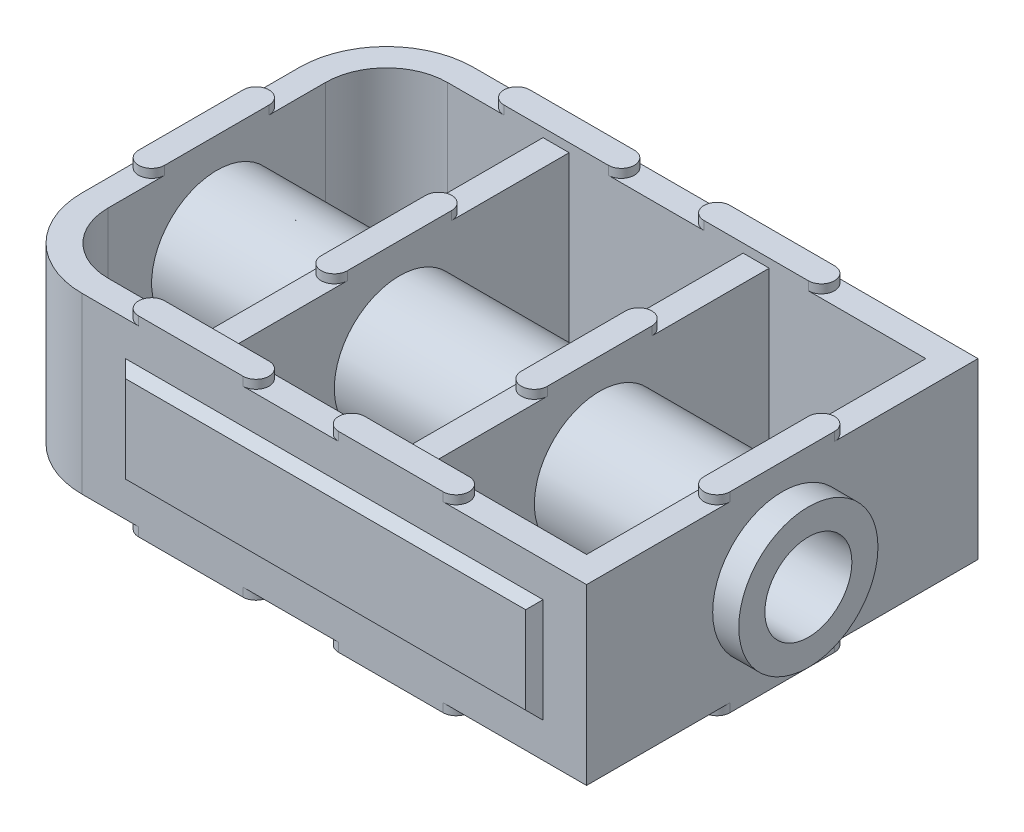
SolidWorks part; units mm, degrees
ref_plane "Front Plane" through (0, 0, 0) normal (0, 0, 1) x (1, 0, 0)
ref_plane "Top Plane" through (0, 0, 0) normal (0, 1, 0) x (1, 0, 0)
ref_plane "Right Plane" through (0, 0, 0) normal (1, 0, 0) x (0, 0, -1)
sketch "Sketch1" plane through (0, 0, 0) normal (0, 1, 0) x (1, 0, 0)
  line L0 (-3, 19.5) -> (-21, 19.5)
  line L1 (0, -22.5) -> (-58, -22.5)
  line L2 (0, -22.5) -> (0, 22.5)
  line L3 (0, 22.5) -> (-58, 22.5)
  line L4 (-68, -12.5) -> (-68, 12.5)
  line L5 (-65, -12.5) -> (-65, 12.5)
  line L6 (-3, -19.5) -> (-21, -19.5)
  line L7 (-3, -19.5) -> (-3, 19.5)
  line L8 (-47, 19.5) -> (-47, -19.5)
  line L9 (-44, -19.5) -> (-44, 19.5)
  line L10 (-24, -19.5) -> (-24, 19.5)
  line L11 (-21, 19.5) -> (-21, -19.5)
  line L12 (-47, 19.5) -> (-58, 19.5)
  line L13 (-47, -19.5) -> (-58, -19.5)
  line L14 (-3, 19.5) -> (-58, 19.5) construction
  line L15 (-24, -19.5) -> (-44, -19.5)
  line L16 (-3, -19.5) -> (-58, -19.5) construction
  line L17 (-24, 19.5) -> (-44, 19.5)
  arc A0 (-58, -22.5) -> (-68, -12.5) centre (-58, -12.5) cw
  arc A1 (-58, 22.5) -> (-68, 12.5) centre (-58, 12.5) ccw
  arc A2 (-58, 19.5) -> (-65, 12.5) centre (-58, 12.5) ccw
  arc A3 (-58, -19.5) -> (-65, -12.5) centre (-58, -12.5) cw
  point P4 (0, 0)
  point P8 (-68, -22.5)
  point P11 (-68, 22.5)
  dimension "D3" = 10
  dimension "D1" = 68
  dimension "D2" = 45
  dimension "D5" = 3
  dimension "D6" = 3
  dimension "D7" = 18
  dimension "D8" = 18
  dimension "D4" = 3
extrude "Boss-Extrude1" add sketch "Sketch1" along normal mid plane 20
sketch "Sketch3" plane through (0, 0, 0) normal (1, 0, 0) x (0, 0, -1)
  line L0 (-22.5, 10) -> (-22.5, -10) construction
  circle A0 centre (0, 0) radius 7.5
  point P7 (-22.5, 0)
  dimension "D1" = 15
extrude "Boss-Extrude3" add sketch "Sketch3" against normal up to surface (65 mm away) up to face at (-65, 0, 0)
sketch "Sketch4" plane through (0, 0, 0) normal (1, 0, 0) x (0, 0, -1)
  line L0 (-22.5, 10) -> (-22.5, -10) construction
  circle A0 centre (0, 0) radius 5
  point P7 (-22.5, 0)
  dimension "D1" = 10
extrude "Cut-Extrude1" cut sketch "Sketch4" against normal up to surface (68 mm away) up to face at (-68, 0, 0)
sketch "Sketch5" plane through (-68, 0, 0) normal (-1, 0, 0) x (0, 0, 1)
  line L1 (3.4641, 6) -> (-3.4641, 6)
  line L2 (-3.4641, 6) -> (-6.9282, 0)
  line L3 (-6.9282, 0) -> (-3.4641, -6)
  line L4 (-3.4641, -6) -> (3.4641, -6)
  line L5 (3.4641, -6) -> (6.9282, 0)
  line L6 (6.9282, 0) -> (3.4641, 6)
  circle A0 centre (0, 0) radius 6 construction
  dimension "D1" = 12
extrude "Cut-Extrude2" cut sketch "Sketch5" against normal blind 5
sketch "Sketch6" plane through (0, 0, 0) normal (1, 0, 0) x (0, 0, -1)
  circle A0 centre (0, 0) radius 5 construction
  circle A1 centre (0, 0) radius 5
  circle A2 centre (0, 0) radius 8
  dimension "D1" = 16
extrude "Boss-Extrude4" add sketch "Sketch6" along normal blind 3
sketch "Sketch7" plane through (0, 10, 0) normal (0, 1, 0) x (1, 0, 0)
  line L0 (-16.5, 21) -> (-28.5, 21) construction
  line L1 (-16.5, 19.5) -> (-28.5, 19.5)
  line L2 (-16.5, 22.5) -> (-28.5, 22.5)
  line L3 (-51.5, 21) -> (-39.5, 21) construction
  line L4 (-51.5, 22.5) -> (-39.5, 22.5)
  line L5 (-51.5, 19.5) -> (-39.5, 19.5)
  line L6 (0, 0) -> (-78.1897, 0) construction
  line L7 (-24, 19.5) -> (-44, 19.5) construction
  line L8 (0, 22.5) -> (-58, 22.5) construction
  line L9 (-44, 19.5) -> (-44, -19.5) construction
  line L10 (-16.5, -21) -> (-28.5, -21) construction
  line L11 (-16.5, -19.5) -> (-28.5, -19.5)
  line L12 (-16.5, -22.5) -> (-28.5, -22.5)
  line L13 (-51.5, -21) -> (-39.5, -21) construction
  line L14 (-51.5, -22.5) -> (-39.5, -22.5)
  line L15 (-51.5, -19.5) -> (-39.5, -19.5)
  line L16 (-66.5, -6) -> (-66.5, 6) construction
  line L17 (-68, -6) -> (-68, 6)
  line L18 (-65, -6) -> (-65, 6)
  line L19 (-22.5, -6) -> (-22.5, 6) construction
  line L20 (-24, -6) -> (-24, 6)
  line L21 (-21, -6) -> (-21, 6)
  line L22 (-45.5, -6) -> (-45.5, 6) construction
  line L23 (-47, -6) -> (-47, 6)
  line L24 (-44, -6) -> (-44, 6)
  line L25 (-1.5, -6) -> (-1.5, 6) construction
  line L26 (-3, -6) -> (-3, 6)
  line L27 (0, -6) -> (0, 6)
  line L28 (-68, 12.5) -> (-68, -12.5) construction
  line L29 (0, -8) -> (0, 8) construction
  line L30 (-21, 19.5) -> (-21, -19.5) construction
  arc A0 (-16.5, 19.5) -> (-16.5, 22.5) centre (-16.5, 21) ccw
  arc A1 (-28.5, 22.5) -> (-28.5, 19.5) centre (-28.5, 21) ccw
  arc A2 (-51.5, 22.5) -> (-51.5, 19.5) centre (-51.5, 21) ccw
  arc A3 (-39.5, 19.5) -> (-39.5, 22.5) centre (-39.5, 21) ccw
  arc A4 (-16.5, -19.5) -> (-16.5, -22.5) centre (-16.5, -21) cw
  arc A5 (-28.5, -22.5) -> (-28.5, -19.5) centre (-28.5, -21) cw
  arc A6 (-51.5, -22.5) -> (-51.5, -19.5) centre (-51.5, -21) cw
  arc A7 (-39.5, -19.5) -> (-39.5, -22.5) centre (-39.5, -21) cw
  arc A8 (-68, -6) -> (-65, -6) centre (-66.5, -6) ccw
  arc A9 (-65, 6) -> (-68, 6) centre (-66.5, 6) ccw
  arc A10 (-24, -6) -> (-21, -6) centre (-22.5, -6) ccw
  arc A11 (-21, 6) -> (-24, 6) centre (-22.5, 6) ccw
  arc A12 (-47, -6) -> (-44, -6) centre (-45.5, -6) ccw
  arc A13 (-44, 6) -> (-47, 6) centre (-45.5, 6) ccw
  arc A14 (-3, -6) -> (0, -6) centre (-1.5, -6) ccw
  arc A15 (0, 6) -> (-3, 6) centre (-1.5, 6) ccw
  point P2 (-22.5, 21)
  point P9 (-45.5, 21)
  point P17 (-66.5, 0)
  point P26 (-22.5, 19.5)
  point P33 (-22.5, -21)
  point P40 (-45.5, -21)
  point P48 (-22.5, 0)
  point P55 (-45.5, 0)
  point P62 (-1.5, 0)
  dimension "D5" = 1.5
  dimension "D7" = 1.5
  dimension "D9" = 1.5
  dimension "D11" = 1.5
  dimension "D1" = 12
  dimension "D2" = 12
  dimension "D3" = 1.5
  dimension "D4" = 1.5
  dimension "D6" = 12
  dimension "D8" = 12
  dimension "D10" = 12
  dimension "D12" = 12
extrude "Boss-Extrude5" add sketch "Sketch7" along normal blind 1
mirror "Mirror1" about plane through (0, 0, 0) normal (0, 1, 0) of "Boss-Extrude5"
sketch "Sketch8" plane through (0, 0, 22.5) normal (0, 0, 1) x (1, 0, 0)
  line L0 (0, 10) -> (0, -10) construction
  line L1 (-5, 6) -> (-53, 6)
  line L2 (-5, 6) -> (-5, -6)
  line L3 (-5, -6) -> (-53, -6)
  line L4 (-53, 6) -> (-53, -6)
  line L5 (-58, 10) -> (-58, -10) construction
  line L6 (-16.5, 10) -> (0, 10) construction
  point P4 (-5, 0)
  dimension "D1" = 5
  dimension "D2" = 5
  dimension "D3" = 4
extrude "Boss-Extrude6" add sketch "Sketch8" along normal blind 1
chamfer "Chamfer1" distance 1 angle 45 4 edges at (-53, 0, 23.5) (-29, -6, 23.5) (-5, 0, 23.5) (-29, 6, 23.5)
mirror "Mirror2" about plane through (0, 0, 0) normal (0, 0, 1) of "Chamfer1", "Boss-Extrude6"
